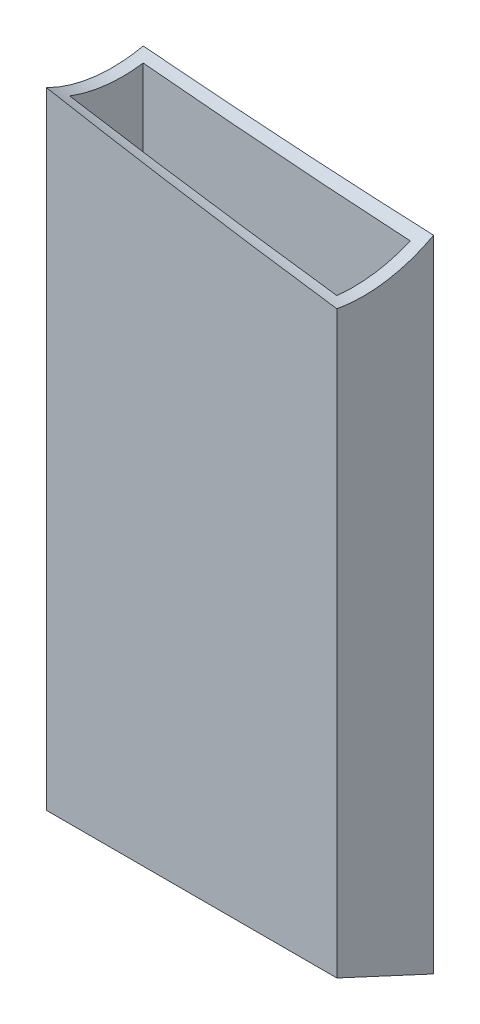
SolidWorks part; units mm, degrees
note: '?' marks a value the reader was unsure of.
material "A500"
ref_plane "Front Plane" through (0, 0, 0) normal (0, 0, 1) x (1, 0, 0)
ref_plane "Top Plane" through (0, 0, 0) normal (0, 1, 0) x (1, 0, 0)
ref_plane "Right Plane" through (0, 0, 0) normal (1, 0, 0) x (0, 0, -1)
sketch "Sketch1" plane through (0, 0, 0) normal (0, 1, 0) x (1, 0, 0)
  line L0 (0, 9.652) -> (0, 12.7) construction
  line L1 (-38.1, 12.7) -> (38.1, 12.7)
  line L2 (-38.1, 12.7) -> (-38.1, -12.7)
  line L3 (-38.1, -12.7) -> (38.1, -12.7)
  line L4 (38.1, 12.7) -> (38.1, -12.7)
  line L5 (-35.052, 9.652) -> (35.052, 9.652)
  line L6 (-35.052, 9.652) -> (-35.052, -9.652)
  line L7 (-35.052, -9.652) -> (35.052, -9.652)
  line L8 (35.052, 9.652) -> (35.052, -9.652)
  line L9 (35.052, 0) -> (38.1, 0) construction
  line L10 (0, -9.652) -> (0, -12.7) construction
  line L11 (-35.052, 0) -> (-38.1, 0) construction
  line L12 (0, 9.652) -> (0, 0) construction
  line L13 (0, 0) -> (-35.052, 0) construction
  dimension "D1" = 76.2
  dimension "D2" = 25.4
  dimension "D3" = 3.048
extrude "Boss-Extrude1" add sketch "Sketch1" along normal up to vertex (200 mm away)
ref_plane "Plane1" through (0, 0, 0) normal (0, 0, 1) x (1, 0, 0)
sketch "Sketch2" plane through (0, 0, 0) normal (0, 0, 1) x (1, 0, 0)
  line L0 (0, 0) -> (0, 200) construction
  line L1 (-38.1, 200) -> (38.1, 200) construction
  line L2 (0, 100) -> (-38.1, 100) construction
  line L3 (-38.1, 200) -> (-38.1, 0) construction
  line L4 (0, 100) -> (38.1, 100) construction
  line L5 (38.1, 200) -> (38.1, 0) construction
ref_axis "Axis1" through (0, 200, 0) along (0, -1, 0)?
sketch "Sketch3" plane through (0, 0, 0) normal (0, -1, 0) x (1, 0, 0)
  line L0 (-35.052, -9.652) -> (-35.052, 9.652) construction
  line L1 (35.052, -9.652) -> (-35.052, -9.652) construction
  line L2 (-35.052, 9.652) -> (35.052, 9.652) construction
  line L3 (35.052, 9.652) -> (35.052, -9.652) construction
  line L4 (-38.1, 12.7) -> (-38.1, -12.7)
  line L5 (-38.1, -12.7) -> (38.1, -12.7)
  line L6 (38.1, -12.7) -> (38.1, 12.7)
  line L7 (38.1, 12.7) -> (-38.1, 12.7)
  line L8 (-38.1, 12.7) -> (-38.1, -12.7)
  line L9 (-38.1, -12.7) -> (38.1, -12.7)
  line L10 (38.1, -12.7) -> (38.1, 12.7)
  line L11 (38.1, 12.7) -> (-38.1, 12.7)
  line L12 (-35.052, -9.652) -> (-35.052, 9.652)
  line L13 (35.052, -9.652) -> (-35.052, -9.652)
  line L14 (-35.052, 9.652) -> (35.052, 9.652)
  line L15 (35.052, 9.652) -> (35.052, -9.652)
  dimension "D1" = 0
extrude "Boss-Extrude2" add sketch "Sketch3" along normal blind 38.1
sketch "Sketch5" plane through (38.1, 0, 0) normal (1, 0, 0) x (0, 0, -1)
  line L1 (-29.2379, 13.5636) -> (-9.6965, -8.2018) construction
  line L2 (-384.0405, -324.8413) -> (0, 0) construction
  line L3 (-29.2379, 13.5636) -> (0, 12.7) construction
  line L4 (0, 0) -> (0, 200) construction
  line L5 (-27.7564, -43.3485) -> (21.2208, -61.9599)
  line L7 (-27.7564, -43.3485) -> (-29.2379, 13.5636)
  line L8 (21.2208, -61.9599) -> (71.3429, -33.0964)
  line L9 (-29.2379, 13.5636) -> (0, 0)
  line L10 (0, 0) -> (71.3429, -33.0964)
  dimension "D1" = 12.7
  dimension "D2" = 12.7
extrude "Cut-Extrude1" cut sketch "Sketch5" against normal through all
ref_plane "Plane2" through (56.8752, 193.5234, 7.6569) normal (-0.9848, 0.1121, -0.1326) x (-0.1316, 0.0164, 0.9912)
sketch "Sketch6" plane through (56.8752, 193.5234, 7.6569) normal (-0.9848, 0.1121, -0.1326) x (-0.1316, 0.0164, 0.9912)
  circle A0 centre (0, 0) radius 38.1 construction
  circle A1 centre (0, 0) radius 38.1
extrude "Cut-Extrude2" cut sketch "Sketch6" along normal up to vertex
equation "\"tubeMainWidth\"= 76.2mm"
equation "\"tubeSecondWidth\"= 25.4mm"
equation "\"tubeThickness\"= 3.048mm"
equation "\"halfMainWidthOfTubing\"= (\"tubeMainWidth\"/2)"
equation "\"D1@Sketch1\"=\"tubeMainWidth\""
equation "\"D2@Sketch1\"=\"tubeSecondWidth\""
equation "\"D3@Sketch1\"=\"tubeThickness\""
equation "\"D1@Boss-Extrude2\"=\"halfMainWidthOfTubing\""
